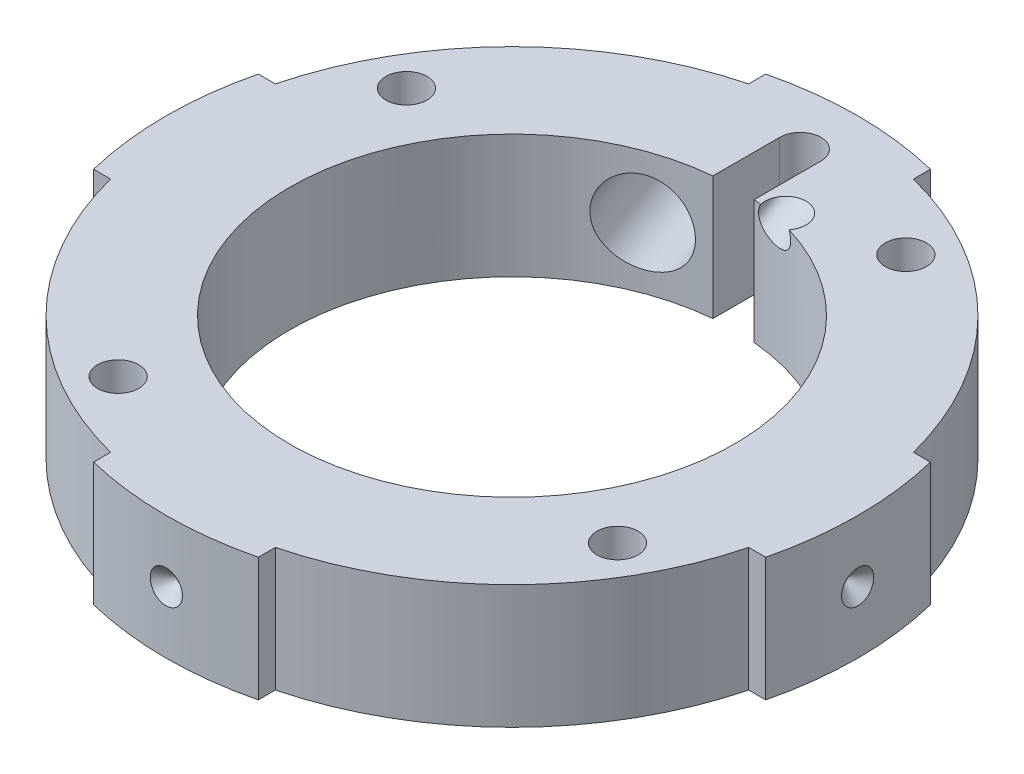
SolidWorks part; units mm, degrees
material "Cast Carbon Steel"
ref_plane "Front Plane" through (0, 0, 0) normal (0, 0, 1) x (1, 0, 0)
ref_plane "Top Plane" through (0, 0, 0) normal (0, 1, 0) x (1, 0, 0)
ref_plane "Right Plane" through (0, 0, 0) normal (1, 0, 0) x (0, 0, -1)
sketch "Sketch1" plane through (0, 0, 0) normal (0, 1, 0) x (1, 0, 0)
  line L0 (0, 0) -> (0, 18.2519) construction
  line L1 (-2.5, 35) -> (-2.5, 26.884)
  line L2 (2.5, 35) -> (2.5, 26.884)
  circle A0 centre (0, 0) radius 27
  circle A1 centre (0, 0) radius 40
  circle A2 centre (0, 3) radius 24 construction
  arc A3 (-2.5, 35) -> (2.5, 35) centre (0, 35) cw
  dimension "D2" = 48
  dimension "D3" = 54
  dimension "D4" = 80
  dimension "D1" = 3
  dimension "D5" = 5
  dimension "D6" = 35
extrude "Boss-Extrude1" add sketch "Sketch1" along normal blind 15 contours A1 L1 A3 L2 A0 region at (-38.8686, 0, 0)
sketch "Sketch2" plane through (0, 0, 0) normal (0, 1, 0) x (1, 0, 0)
  line L0 (-10, 38.7298) -> (-10, 40.7922)
  line L1 (10, 38.7298) -> (10, 40.7922)
  line L2 (0, 0) -> (0, 56.9042) construction
  arc A0 (-10, 40.7922) -> (10, 40.7922) centre (0, 0) cw
  arc A1 (-10, 38.7298) -> (10, 38.7298) centre (0, 0) cw
  circle A2 centre (0, 0) radius 40 construction
  dimension "D2" = 42
  dimension "D1" = 20
extrude "Boss-Extrude2" add sketch "Sketch2" along normal blind 15
pattern_circular "CirPattern1" count 4 over 360 about axis through (0, 15, 0) along (0, -1, 0) of "Boss-Extrude2"
ref_plane "Plane1" through (-14.3648, 0, -39.4671) normal (-0.342, 0, -0.9397) x (0, -1, 0)
sketch "Sketch3" plane through (-14.3648, 0, -39.4671) normal (-0.342, 0, -0.9397) x (0, -1, 0)
  circle A0 centre (-7.5, 0) radius 5
  dimension "D1" = 10
  dimension "D2" = 7.5
extrude "Cut-Extrude1" cut sketch "Sketch3" against normal up to next
sketch "Sketch5" plane through (0, 15, 0) normal (0, 1, 0) x (1, 0, 0)
  line L0 (5.8215, 27.3881) -> (0, 0) construction
  line L1 (0, 0) -> (0, 18.4446) construction
  circle A0 centre (5.8215, 27.3881) radius 2.5
  dimension "D1" = 5
  dimension "D2" = 12
  dimension "D3" = 28
ref_plane "Plane3" through (0, 12, 0) normal (0, 1, 0) x (1, 0, 0)
sketch "Sketch6" plane through (0, 12, 0) normal (0, 1, 0) x (1, 0, 0)
  line L0 (0, 0) -> (4.9899, 23.4755) construction
  line L2 (0, 23.791) -> (0, 0) construction
  circle A0 centre (4.9899, 23.4755) radius 3
  arc A1 (-2.5, 26.884) -> (2.5, 26.884) centre (0, 0) ccw construction
  dimension "D2" = 6
  dimension "D1" = 12
loft "Cut-Loft1" cut profiles "Sketch5", "Sketch6" connector at (3.5142, 15, -26.4256) connector at (2.075, 12, -24.185)
sketch "Sketch7" plane through (0, 15, 0) normal (0, 1, 0) x (1, 0, 0)
  line L0 (0, 0) -> (0, 44.8528) construction
  line L1 (0, 0) -> (23.2835, 40.3282) construction
  circle A0 centre (0, 0) radius 35 construction
  circle A1 centre (17.5, 30.3109) radius 2.5
  circle A2 centre (30.3109, -17.5) radius 2.5
  circle A3 centre (-17.5, -30.3109) radius 2.5
  circle A4 centre (-30.3109, 17.5) radius 2.5
  point P16 (0, 0)
  dimension "D1" = 5
  dimension "D3" = 70
  dimension "D2" = 30
  dimension "D4" = 4
extrude "Cut-Extrude2" cut sketch "Sketch7" against normal up to next
sketch "Sketch9" plane through (0, 0, 0) normal (1, 0, 0) x (0, 0, -1)
  line L0 (0, 0) -> (0, 24.7398) construction
  line L1 (-10, 0) -> (10, 0) construction
  line L2 (0, 7.5) -> (48.6314, 7.5) construction
  line L3 (42, 7.5) -> (42, 5.5)
  line L5 (42, 0) -> (42, 15) construction
  line L6 (42, 5.5) -> (40, 7.5)
  line L7 (40, 7.5) -> (42, 7.5)
  dimension "D1" = 7.5
  dimension "D3" = 45
  dimension "D4" = 2
revolve "Cut-Revolve4" cut sketch "Sketch9" angle 360 about L7
pattern_circular "CirPattern2" count 4 over 360 about axis through (0, 15, 0) along (0, -1, 0) of "Cut-Revolve4"
